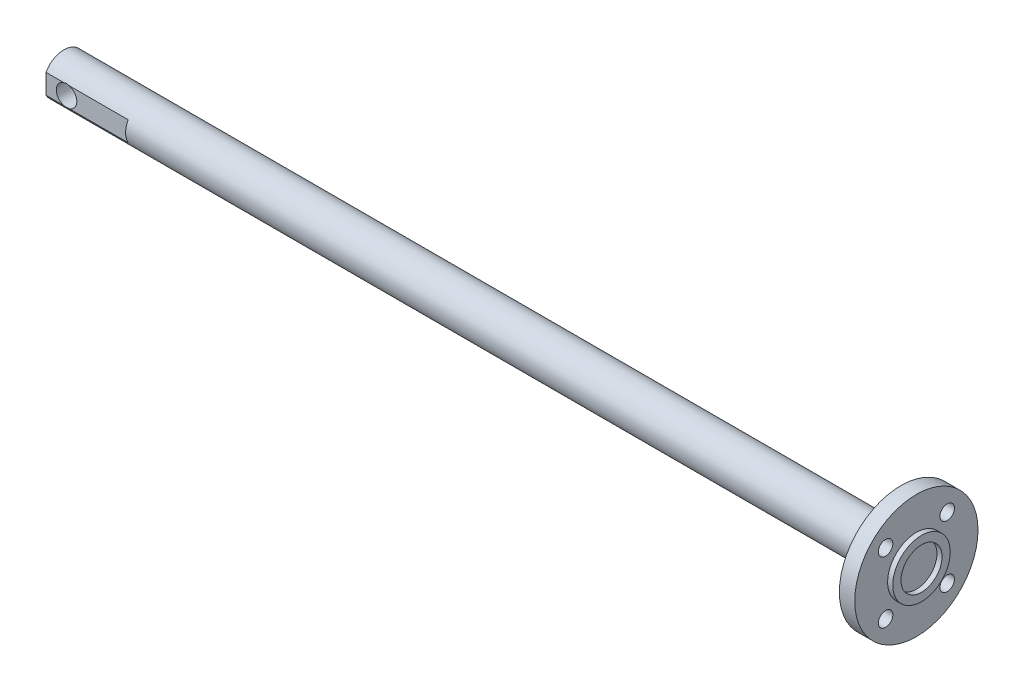
SolidWorks part; units mm, degrees
ref_plane "Front Plane" through (0, 0, 0) normal (0, 0, 1) x (1, 0, 0)
ref_plane "Top Plane" through (0, 0, 0) normal (0, 1, 0) x (1, 0, 0)
ref_plane "Right Plane" through (0, 0, 0) normal (1, 0, 0) x (0, 0, -1)
sketch "Sketch1" plane through (0, 0, 0) normal (1, 0, 0) x (0, 0, -1)
  circle A0 centre (0, 0) radius 19.05
  dimension "D1" = 38.1
extrude "Boss-Extrude1" add sketch "Sketch1" along normal blind 263.525
sketch "Sketch2" plane through (0, 0, 0) normal (0, 0, 1) x (1, 0, 0)
  line L0 (-16.5207, 0) -> (279.5841, 0) construction
  line L1 (0, 6.35) -> (258.7625, 6.35)
  line L2 (258.7625, 6.35) -> (258.7625, 19.05)
  line L3 (263.525, 19.05) -> (0, 19.05) construction
  line L4 (258.7625, 19.05) -> (0, 19.05)
  line L5 (0, 19.05) -> (0, 6.35)
  line L6 (263.525, -19.05) -> (263.525, 19.05) construction
  dimension "D1" = 6.35
  dimension "D2" = 4.7625
revolve "Cut-Revolve1" cut sketch "Sketch2" angle 360 about L0
sketch "Sketch8" plane through (0, 0, 0) normal (0, 1, 0) x (1, 0, 0)
  line L0 (-5.5022, 0) -> (24.2999, 0) construction
  line L1 (0, 6.35) -> (25.4, 6.35)
  line L2 (0, 6.35) -> (0, 5.5562)
  line L3 (0, 5.5562) -> (25.4, 5.5562)
  line L4 (25.4, 6.35) -> (25.4, 5.5562)
  line L5 (25.4, -6.35) -> (25.4, -5.5562)
  line L6 (0, -5.5562) -> (25.4, -5.5562)
  line L7 (0, -6.35) -> (0, -5.5562)
  line L8 (0, -6.35) -> (25.4, -6.35)
  dimension "D1" = 25.4
  dimension "D2" = 0.7937
extrude "Cut-Extrude1" cut sketch "Sketch8" against normal through all and the other way through all
hole_wizard "1 (1) Diameter Hole2" positions "Sketch10" profile "Sketch11" hole size "1" standard "ANSI Inch" end condition through all
sketch "Sketch10" plane through (0, 0, -5.5562) normal (0, 0, -1) x (-1, 0, 0)
  line L0 (-14.7038, 0) -> (11.7279, 0) construction
  line L2 (0, 3.0742) -> (0, -3.0742) construction
  point P0 (-6.35, 0)
  dimension "D1" = 6.35
sketch "Sketch11" plane through (6.35, 0, -5.5562) normal (1, 0, 0) x (0, 1, 0)
  line L0 (0, 0) -> (0, 24.6062)
  line L1 (0, 24.6062) -> (3.175, 24.6062)
  line L2 (3.175, 24.6062) -> (3.175, 0)
  line L5 (3.175, 0) -> (0, 0)
  line L11 (0, -6.35) -> (0, 107.95) construction
  dimension "Thru Hole Dia." = 6.35
  dimension "Thru Hole Depth" = 24.6062
hole_wizard "#16 (0.177) Diameter Hole1" positions "Sketch14" profile "Sketch13" hole size "#16" standard "ANSI Inch"
sketch "Sketch14" plane through (258.7625, 0, 0) normal (-1, 0, 0) x (0, 0, 1)
  line L1 (-9.525, -9.525) -> (9.525, -9.525) construction
  line L2 (-9.525, -9.525) -> (-9.525, 9.525) construction
  line L3 (-9.525, 9.525) -> (9.525, 9.525) construction
  line L4 (9.525, -9.525) -> (9.525, 9.525) construction
  circle A0 centre (0, 0) radius 19.05 construction
  circle A1 centre (0, 0) radius 19.05 construction
  point P2 (9.525, 9.525)
  point P85 (-9.525, -9.525)
  point P86 (-9.525, 9.525)
  point P87 (9.525, -9.525)
  dimension "D1" = 19.05
  dimension "D2" = 9.525
  dimension "D3" = 9.525
sketch "Sketch13" plane through (258.7625, 9.525, 9.525) normal (0, 1, 0) x (0, 0, 1)
  line L0 (0, 0) -> (0, 26.7507)
  line L1 (0, 26.7507) -> (2.2479, 25.4)
  line L2 (2.2479, 25.4) -> (2.2479, 0)
  line L5 (2.2479, 0) -> (0, 0)
  line L10 (0, 26.7507) -> (-2.2479, 25.4) construction
  line L11 (0, -6.35) -> (0, 107.95) construction
  dimension "Hole Dia." = 4.4958
  dimension "Hole Depth" = 25.4
  dimension "Drill Angle" = 118
sketch "Sketch15" plane through (263.525, 0, 0) normal (1, 0, 0) x (0, 0, -1)
  circle A0 centre (0, 0) radius 8.89
  circle A1 centre (0, 0) radius 6.35
  dimension "D1" = 17.78
  dimension "D2" = 2.54
extrude "Boss-Extrude2" add sketch "Sketch15" along normal blind 1.5875
